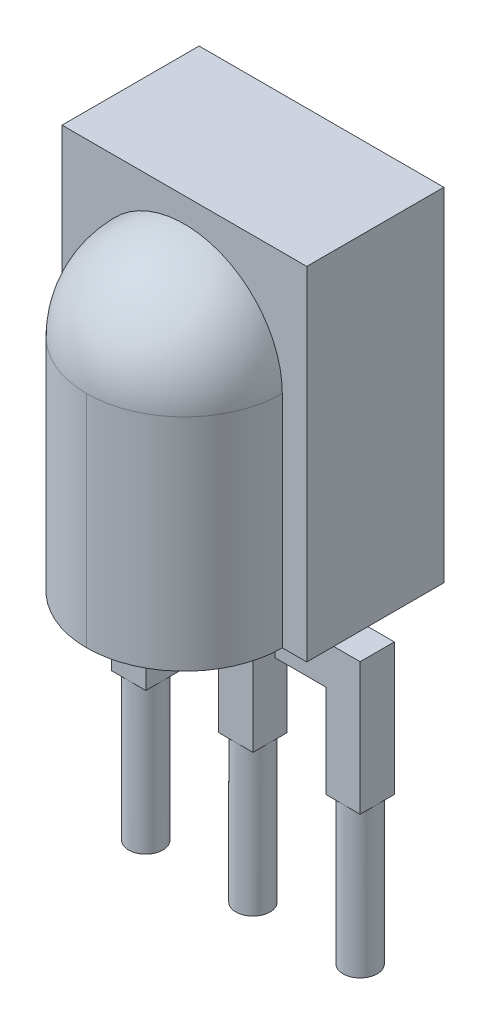
SolidWorks part; units mm, degrees
ref_plane "Piano frontale" through (0, 0, 0) normal (0, 0, 1) x (1, 0, 0)
ref_plane "Piano superiore" through (0, 0, 0) normal (0, 1, 0) x (1, 0, 0)
ref_plane "Piano destro" through (0, 0, 0) normal (1, 0, 0) x (0, 0, -1)
sketch "Schizzo1" plane through (0, 0, 0) normal (0, 1, 0) x (1, 0, 0)
  line L1 (0, 0) -> (5, 0)
  line L2 (0, 0) -> (0, 2.8)
  line L3 (0, 2.8) -> (5, 2.8)
  line L4 (5, 0) -> (5, 2.8)
  dimension "D1" = 5
  dimension "D2" = 2.8
extrude "Estrusione-Estrusione1" add sketch "Schizzo1" along normal blind 7
sketch "Schizzo2" plane through (0, 0, 0) normal (0, 0, 1) x (1, 0, 0)
  line L1 (0, 0) -> (5, 0) construction
  line L2 (0.5, 0) -> (4.5, 0)
  line L3 (0.5, 4.5) -> (0.5, 0)
  line L4 (4.5, 4.5) -> (4.5, 0)
  line L6 (2.5, 7) -> (2.5, 0) construction
  line L7 (0, 7) -> (5, 7) construction
  arc A0 (0.5, 4.5) -> (4.5, 4.5) centre (2.5, 4.5) cw
  dimension "D1" = 4.5
extrude "Estrusione-Estrusione2" add sketch "Schizzo2" along normal blind 2
fillet "Raccordo1" radius 2 3 edges at (4.5, 2.25, 2) (0.5, 2.25, 2) (2.5, 6.5, 2)
sketch "Schizzo3" plane through (0, 0, 0) normal (0, -1, 0) x (-1, 0, 0)
  line L0 (-2.5, -2) -> (-2.5, 2.8) construction
  line L1 (-5, 2.8) -> (0, 2.8) construction
  line L2 (0, 1.4) -> (-5, 1.4) construction
  line L3 (0, 2.8) -> (0, 0) construction
  line L4 (-5, 0) -> (-5, 2.8) construction
  line L5 (-1.35, 1.05) -> (-1.35, 1.75) construction
  line L6 (-1, 1.05) -> (-1.7, 1.05)
  line L7 (-1, 1.05) -> (-1, 1.75)
  line L8 (-1, 1.75) -> (-1.7, 1.75)
  line L9 (-1.7, 1.05) -> (-1.7, 1.75)
  line L10 (-2.85, 1.05) -> (-2.15, 1.05)
  line L11 (-2.15, 1.05) -> (-2.15, 1.75)
  line L12 (-2.15, 1.75) -> (-2.85, 1.75)
  line L13 (-2.85, 1.05) -> (-2.85, 1.75)
  line L14 (-3.3, 1.05) -> (-3.3, 1.75)
  line L15 (-4, 1.75) -> (-3.3, 1.75)
  line L16 (-4, 1.05) -> (-4, 1.75)
  line L17 (-4, 1.05) -> (-3.3, 1.05)
  point P22 (-2.5, 1.75)
  point P23 (-2.5, 1.05)
  dimension "D1" = 0.7
  dimension "D2" = 0.7
  dimension "D3" = 0.35
  dimension "D4" = 0.35
extrude "Estrusione-Estrusione3" add sketch "Schizzo3" along normal blind 0.5
sketch "Schizzo4" plane through (0, -0.5, 0) normal (0, -1, 0) x (-1, 0, 0)
  line L0 (-1, 1.75) -> (-1.7, 1.75) construction
  line L1 (-1.7, 1.05) -> (0.04, 1.05)
  line L2 (-1.7, 1.05) -> (-1.7, 1.75)
  line L3 (-1.7, 1.75) -> (0.04, 1.75)
  line L4 (0.04, 1.05) -> (0.04, 1.75)
  line L5 (-2.5, 1.05) -> (-2.5, 1.75) construction
  line L6 (-2.85, 1.05) -> (-2.15, 1.05) construction
  line L7 (-2.15, 1.75) -> (-2.85, 1.75) construction
  line L8 (-0.31, 1.05) -> (-0.31, 1.75) construction
  line L9 (-2.15, 1.05) -> (-2.85, 1.05)
  line L10 (-2.15, 1.05) -> (-2.15, 1.75)
  line L11 (-2.15, 1.75) -> (-2.85, 1.75)
  line L12 (-4.69, 1.05) -> (-4.69, 1.75) construction
  line L13 (-2.85, 1.05) -> (-2.85, 1.75)
  line L14 (-5.04, 1.05) -> (-5.04, 1.75)
  line L15 (-3.3, 1.75) -> (-5.04, 1.75)
  line L16 (-3.3, 1.05) -> (-3.3, 1.75)
  line L17 (-3.3, 1.05) -> (-5.04, 1.05)
  dimension "D1" = 0.35
  dimension "D2" = 2.54
extrude "Estrusione-Estrusione4" add sketch "Schizzo4" along normal blind 0.8
sketch "Schizzo5" plane through (0, -1.3, 0) normal (0, -1, 0) x (1, 0, 0)
  line L0 (-0.04, -1.75) -> (1.7, -1.75) construction
  line L1 (-0.04, -1.05) -> (0.66, -1.05)
  line L2 (-0.04, -1.05) -> (-0.04, -1.75)
  line L3 (-0.04, -1.75) -> (0.66, -1.75)
  line L4 (0.66, -1.05) -> (0.66, -1.75)
  line L5 (3.3, -1.75) -> (5.04, -1.75) construction
  line L6 (5.04, -1.05) -> (4.34, -1.05)
  line L7 (5.04, -1.05) -> (5.04, -1.75)
  line L8 (5.04, -1.75) -> (4.34, -1.75)
  line L9 (4.34, -1.05) -> (4.34, -1.75)
  line L11 (2.15, -1.05) -> (2.85, -1.05)
  line L12 (2.15, -1.05) -> (2.15, -1.75)
  line L13 (2.15, -1.75) -> (2.85, -1.75)
  line L14 (2.85, -1.05) -> (2.85, -1.75)
  dimension "D1" = 0.7
  dimension "D2" = 0.7
extrude "Estrusione-Estrusione5" add sketch "Schizzo5" along normal blind 1.9
sketch "Schizzo6" plane through (0, -3.2, 0) normal (0, -1, 0) x (1, 0, 0)
  line L0 (-0.04, -1.4) -> (0.66, -1.4) construction
  line L1 (-0.04, -1.05) -> (-0.04, -1.75) construction
  line L2 (0.66, -1.75) -> (0.66, -1.05) construction
  line L3 (2.15, -1.4) -> (2.85, -1.4) construction
  line L4 (2.15, -1.05) -> (2.15, -1.75) construction
  line L5 (2.85, -1.75) -> (2.85, -1.05) construction
  line L6 (4.34, -1.4) -> (5.04, -1.4) construction
  line L7 (4.34, -1.05) -> (4.34, -1.75) construction
  line L8 (5.04, -1.75) -> (5.04, -1.05) construction
  circle A0 centre (0.31, -1.4) radius 0.35
  circle A1 centre (2.5, -1.4) radius 0.35
  circle A2 centre (4.69, -1.4) radius 0.35
extrude "Estrusione-Estrusione6" add sketch "Schizzo6" along normal blind 3
